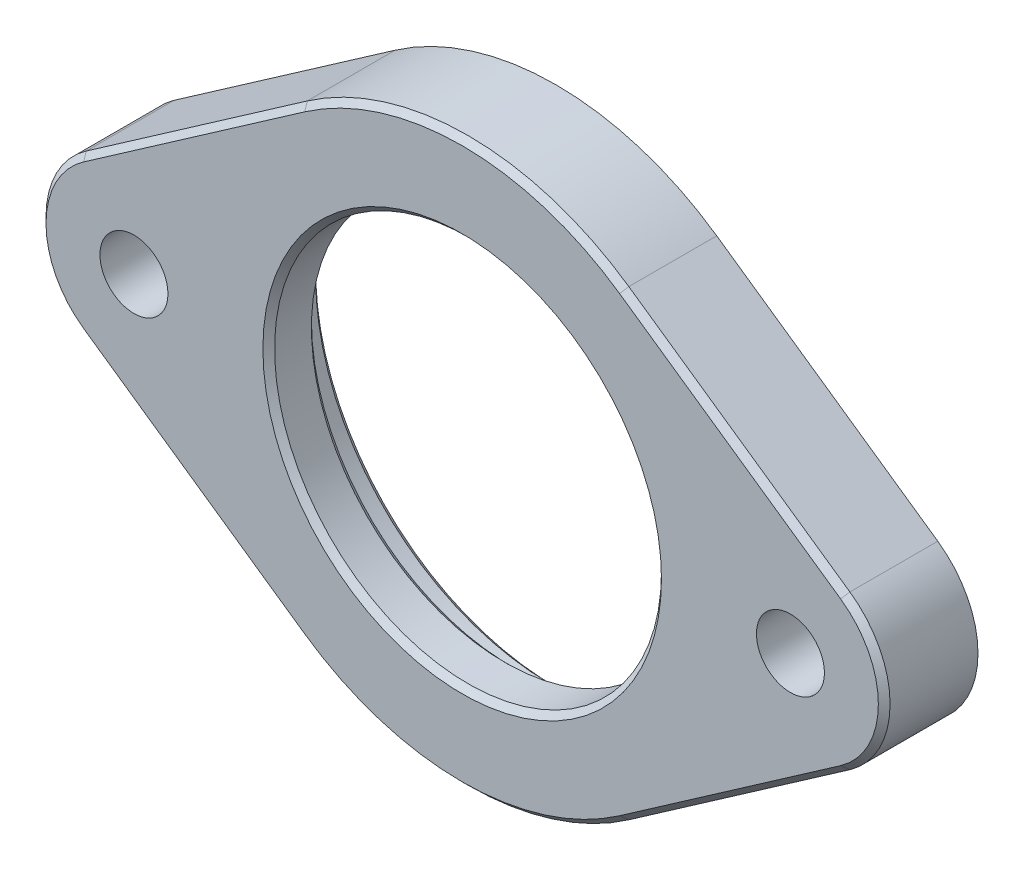
SolidWorks part; units mm, degrees
material "ABS"
ref_plane "Front Plane" through (0, 0, 0) normal (0, 0, 1) x (1, 0, 0)
ref_plane "Top Plane" through (0, 0, 0) normal (0, 1, 0) x (1, 0, 0)
ref_plane "Right Plane" through (0, 0, 0) normal (1, 0, 0) x (0, 0, -1)
sketch "Sketch1" plane through (0, 0, 0) normal (0, 0, 1) x (1, 0, 0)
  line L0 (-14, 0) -> (14, 0)
  line L1 (-6.8571, -9.8478) -> (-16.2857, -3.2826)
  line L2 (-6.8571, 9.8478) -> (-16.2857, 3.2826)
  line L3 (6.8571, 9.8478) -> (16.2857, 3.2826)
  line L4 (6.8571, -9.8478) -> (16.2857, -3.2826)
  circle A0 centre (0, 0) radius 8.25
  circle A1 centre (0, 0) radius 10
  circle A2 centre (0, 0) radius 12
  circle A3 centre (-14, 0) radius 4
  circle A4 centre (14, 0) radius 4
  point P7 (0, 0)
  dimension "D1" = 16.5
  dimension "D2" = 20
  dimension "D3" = 2
  dimension "D4" = 8
  dimension "D5" = 28
extrude "Boss-Extrude1" add sketch "Sketch1" along normal blind 4 contours A3 L0 A2 L2 | A3 L1 A2 L0 | A3 | A4 L3 A2 L0 | A4 | A4 L0 A2 L4 | A2 region at (14.6154, 0, 0) region at (11.8356, 5.4155, 0) region at (11.8356, -5.4155, 0) region at (-14.6154, 0, 0) region at (-11.8356, 5.4155, 0) region at (-11.8356, -5.4155, 0)
extrude "Cut-Extrude1" cut sketch "Sketch1<4>" against normal through all both and the other way through all contours L0 A0 | L0 A0 region at (0, -3.5014, 0) region at (0, 3.5014, 0)
sketch "Sketch1<4>" plane through (0, 0, 0) normal (0, 0, 1) x (1, 0, 0) same geometry as "Sketch1"
extrude "Cut-Extrude2" cut sketch "Sketch1<6>" along normal blind 1.93 and the other way through all contours A1
sketch "Sketch1<6>" plane through (0, 0, 0) normal (0, 0, 1) x (1, 0, 0) same geometry as "Sketch1"
hole_wizard "M2.5 Clearance Hole1" positions "Sketch2" profile "Sketch3" hole size "M2.5" standard "ANSI Metric" end condition through all
sketch "Sketch2" plane through (0, 0, 4) normal (0, 0, 1) x (1, 0, 0)
  point P0 (-14, 0)
  point P3 (14, 0)
sketch "Sketch3" plane through (-14, 0, 4) normal (1, 0, 0) x (0, -1, 0)
  line L0 (0, 0) -> (0, 4)
  line L1 (0, 4) -> (1.45, 4)
  line L2 (1.45, 4) -> (1.45, 0)
  line L5 (1.45, 0) -> (0, 0)
  line L11 (0, -6.35) -> (0, 107.95) construction
  dimension "Thru Hole Dia." = 2.9
  dimension "Thru Hole Depth" = 4
chamfer "Chamfer1" distance 0.25 angle 45 12 edges at (8.25, 0, 4) (8.25, 0, 1.93) (10, 0, 0) (10, 0, 1.93) (0, -12, 4) (11.5714, -6.5652, 4) (-11.5714, -6.5652, 4) (18, 0, 4) (-18, 0, 4) (11.5714, 6.5652, 4) (-11.5714, 6.5652, 4) (0, 12, 4)
